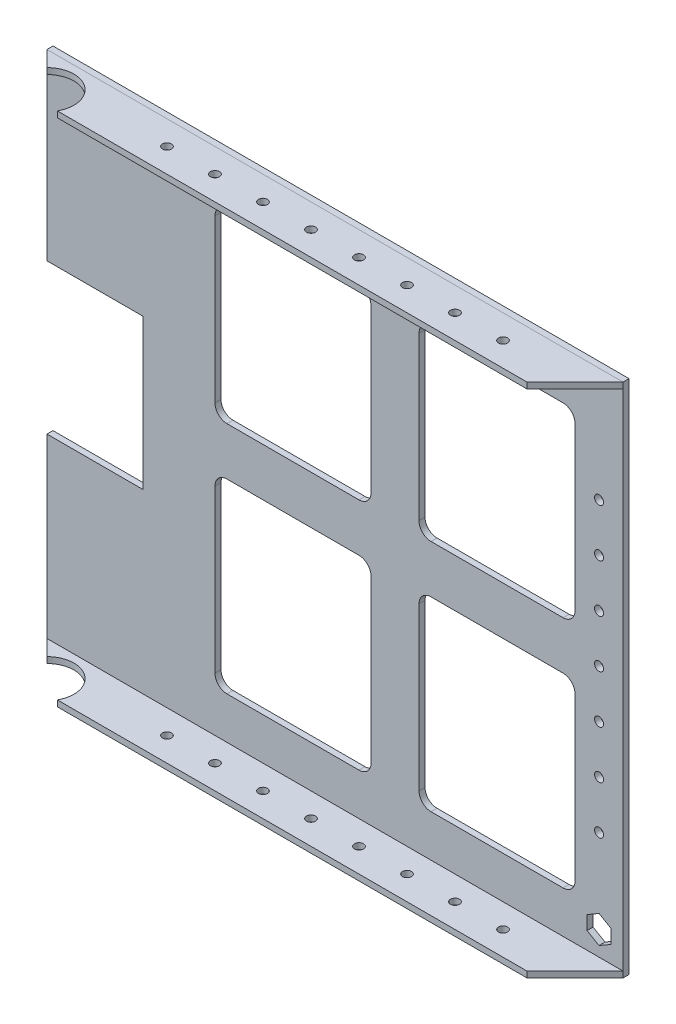
SolidWorks part; units mm, degrees
ref_plane "Front Plane" through (0, 0, 0) normal (0, 0, 1) x (1, 0, 0)
ref_plane "Top Plane" through (0, 0, 0) normal (0, 1, 0) x (1, 0, 0)
ref_plane "Right Plane" through (0, 0, 0) normal (1, 0, 0) x (0, 0, -1)
sketch "Sketch1" plane through (0, 0, 0) normal (0, 0, 1) x (1, 0, 0)
  line L1 (0, 0) -> (304.8, 0)
  line L2 (0, 0) -> (0, 273.05)
  line L3 (0, 273.05) -> (304.8, 273.05)
  line L4 (304.8, 0) -> (304.8, 273.05)
  dimension "D1" = 273.05
  dimension "D2" = 304.8
extrude "Boss-Extrude1" add sketch "Sketch1" along normal blind 3.175
sketch "Sketch2" plane through (0, 0, 3.175) normal (0, 0, 1) x (1, 0, 0)
  line L0 (0, 273.05) -> (0, 0) construction
  line L1 (95.25, 247.65) -> (165.1, 247.65)
  line L2 (88.9, 241.3) -> (88.9, 155.575)
  line L3 (95.25, 149.225) -> (165.1, 149.225)
  line L4 (279.4, 241.3) -> (279.4, 155.575)
  line L5 (95.25, 123.825) -> (165.1, 123.825)
  line L6 (88.9, 117.475) -> (88.9, 31.75)
  line L7 (95.25, 25.4) -> (165.1, 25.4)
  line L8 (279.4, 117.475) -> (279.4, 31.75)
  line L9 (0, 176.2125) -> (50.8, 176.2125)
  line L10 (0, 176.2125) -> (0, 96.8375)
  line L11 (0, 96.8375) -> (50.8, 96.8375)
  line L12 (50.8, 176.2125) -> (50.8, 96.8375)
  line L13 (304.8, 0) -> (304.8, 273.05) construction
  line L14 (304.8, 273.05) -> (0, 273.05) construction
  line L15 (0, 0) -> (304.8, 0) construction
  line L16 (-17.1716, 136.525) -> (403.4647, 136.525) construction
  line L17 (171.45, 241.3) -> (171.45, 155.575)
  line L18 (196.85, 241.3) -> (196.85, 155.575)
  line L19 (171.45, 117.475) -> (171.45, 31.75)
  line L20 (196.85, 117.475) -> (196.85, 31.75)
  line L21 (203.2, 247.65) -> (273.05, 247.65)
  line L22 (203.2, 149.225) -> (273.05, 149.225)
  line L23 (203.2, 123.825) -> (273.05, 123.825)
  line L24 (203.2, 25.4) -> (273.05, 25.4)
  arc A0 (95.25, 123.825) -> (88.9, 117.475) centre (95.25, 117.475) ccw
  arc A1 (88.9, 31.75) -> (95.25, 25.4) centre (95.25, 31.75) ccw
  arc A2 (273.05, 25.4) -> (279.4, 31.75) centre (273.05, 31.75) ccw
  arc A3 (273.05, 123.825) -> (279.4, 117.475) centre (273.05, 117.475) cw
  arc A4 (88.9, 155.575) -> (95.25, 149.225) centre (95.25, 155.575) ccw
  arc A5 (273.05, 149.225) -> (279.4, 155.575) centre (273.05, 155.575) ccw
  arc A6 (273.05, 247.65) -> (279.4, 241.3) centre (273.05, 241.3) cw
  arc A7 (95.25, 247.65) -> (88.9, 241.3) centre (95.25, 241.3) ccw
  arc A8 (196.85, 31.75) -> (203.2, 25.4) centre (203.2, 31.75) ccw
  arc A9 (171.45, 31.75) -> (165.1, 25.4) centre (165.1, 31.75) cw
  arc A10 (196.85, 117.475) -> (203.2, 123.825) centre (203.2, 117.475) cw
  arc A11 (171.45, 117.475) -> (165.1, 123.825) centre (165.1, 117.475) ccw
  arc A12 (196.85, 155.575) -> (203.2, 149.225) centre (203.2, 155.575) ccw
  arc A13 (171.45, 155.575) -> (165.1, 149.225) centre (165.1, 155.575) cw
  arc A14 (196.85, 241.3) -> (203.2, 247.65) centre (203.2, 241.3) cw
  arc A15 (171.45, 241.3) -> (165.1, 247.65) centre (165.1, 241.3) ccw
  point P48 (196.85, 25.4)
  point P53 (196.85, 123.825)
  point P58 (196.85, 149.225)
  point P61 (171.45, 149.225)
  point P64 (196.85, 247.65)
  dimension "D11" = 6.35
  dimension "D15" = 6.35
  dimension "D1" = 25.4
  dimension "D2" = 25.4
  dimension "D3" = 25.4
  dimension "D4" = 25.4
  dimension "D5" = 25.4
  dimension "D6" = 38.1
  dimension "D7" = 38.1
  dimension "D8" = 50.8
  dimension "D9" = 79.375
  dimension "D10" = 136.525
  dimension "D12" = 39.6875
  dimension "D13" = 25.4
  dimension "D14" = 25.4
extrude "Cut-Extrude1" cut sketch "Sketch2" against normal blind 3.175 normal cut yes
sketch "Sketch4" plane through (0, 0, 3.175) normal (0, 0, 1) x (1, 0, 0)
  line L0 (304.8, 0) -> (304.8, 273.05) construction
  line L1 (0, 273.05) -> (304.8, 273.05)
  line L2 (0, 273.05) -> (0, 269.875)
  line L3 (0, 269.875) -> (304.8, 269.875)
  line L4 (304.8, 273.05) -> (304.8, 269.875)
  dimension "D1" = 3.175
sketch "Sketch5" plane through (0, 0, 3.175) normal (0, 0, 1) x (1, 0, 0)
  line L1 (0, 273.05) -> (304.8, 273.05)
  line L2 (0, 273.05) -> (0, 269.875)
  line L3 (0, 269.875) -> (304.8, 269.875)
  line L4 (304.8, 273.05) -> (304.8, 269.875)
base flange "Base-Flange1" sketch "Sketch5" thickness 25.4 reverse thickness direction yes parameters "D1"=0.7366
chamfer "Chamfer1" distance 25.4 angle 45 2 edges at (0, 271.4625, 28.575) (304.8, 271.4625, 28.575)
sketch "Sketch10" plane through (0, 0, 3.175) normal (0, 0, 1) x (1, 0, 0)
  line L0 (304.8, 0) -> (304.8, 273.05) construction
  line L1 (0, 0) -> (304.8, 0)
  line L2 (0, 0) -> (0, 3.175)
  line L3 (0, 3.175) -> (304.8, 3.175)
  line L4 (304.8, 0) -> (304.8, 3.175)
  dimension "D1" = 3.175
base flange "Base-Flange2" sketch "Sketch10" thickness 25.4 reverse thickness direction yes parameters "D1"=0.7366
chamfer "Chamfer2" distance 25.4 angle 45 2 edges at (0, 1.5875, 28.575) (304.8, 1.5875, 28.575)
sketch "Sketch13" plane through (0, 273.05, 0) normal (0, 1, 0) x (1, 0, 0)
  line L1 (304.8, 0) -> (0, 0) construction
  line L3 (0, -3.175) -> (0, 0) construction
  circle A0 centre (18.415, -21.59) radius 14.2875
  dimension "D3" = 18.415
  dimension "D1" = 28.575
  dimension "D2" = 21.59
extrude "Cut-Extrude4" cut sketch "Sketch13" against normal through all normal cut yes
sketch "Sketch14" plane through (0, 0, 0) normal (0, 0, -1) x (-1, 0, 0)
  line L0 (-304.8, 273.05) -> (0, 273.05) construction
  line L1 (-38.1, 273.05) -> (-12.7, 273.05)
  line L2 (-38.1, 273.05) -> (-38.1, 269.875)
  line L3 (-38.1, 269.875) -> (-12.7, 269.875)
  line L4 (-12.7, 273.05) -> (-12.7, 269.875)
  line L5 (0, 273.05) -> (0, 176.2125) construction
  dimension "D1" = 3.175
  dimension "D2" = 25.4
  dimension "D3" = 12.7
sketch "Sketch19" plane through (0, 273.05, 0) normal (0, 1, 0) x (1, 0, 0)
  line L0 (-49.272, -15.875) -> (322.0215, -15.875) construction
  line L1 (279.4, -28.575) -> (30.8786, -28.575) construction
  circle A0 centre (76.2, -15.875) radius 2.3813
  circle A1 centre (101.6, -15.875) radius 2.3813
  circle A2 centre (127, -15.875) radius 2.3813
  circle A3 centre (152.4, -15.875) radius 2.3813
  circle A4 centre (177.8, -15.875) radius 2.3813
  circle A5 centre (203.2, -15.875) radius 2.3813
  circle A6 centre (228.6, -15.875) radius 2.3813
  circle A7 centre (254, -15.875) radius 2.3813
  dimension "D8" = 4.7625
  dimension "D1" = 12.7
  dimension "D2" = 25.4
  dimension "D3" = 25.4
  dimension "D4" = 25.4
  dimension "D5" = 25.4
  dimension "D6" = 25.4
  dimension "D7" = 76.2
  dimension "D9" = 25.4
  dimension "D10" = 25.4
extrude "Cut-Extrude7" cut sketch "Sketch19" against normal through all normal cut yes
sketch "Sketch20" plane through (0, 0, 0) normal (0, 0, -1) x (-1, 0, 0)
  line L0 (-292.1, 281.8115) -> (-292.1, -48.566) construction
  line L1 (-304.8, 0) -> (-304.8, 273.05) construction
  line L2 (-356.7906, 136.525) -> (75.1704, 136.525) construction
  line L3 (0, 273.05) -> (-304.8, 273.05) construction
  circle A0 centre (-292.1, 136.525) radius 2.3813
  circle A1 centre (-292.1, 161.925) radius 2.3813
  circle A2 centre (-292.1, 187.325) radius 2.3813
  circle A3 centre (-292.1, 212.725) radius 2.3813
  circle A4 centre (-292.1, 111.125) radius 2.3813
  circle A5 centre (-292.1, 85.725) radius 2.3813
  circle A6 centre (-292.1, 60.325) radius 2.3813
  dimension "D3" = 4.7625
  dimension "D1" = 12.7
  dimension "D2" = 136.525
  dimension "D4" = 25.4
  dimension "D5" = 50.8
  dimension "D6" = 25.4
  dimension "D7" = 25.4
  dimension "D8" = 25.4
  dimension "D9" = 50.8
extrude "Cut-Extrude8" cut sketch "Sketch20" against normal blind 50.8 normal cut yes
sketch "Sketch21" plane through (0, 3.175, 0) normal (0, 1, 0) x (1, 0, 0)
  circle A0 centre (18.415, -21.59) radius 14.2875
  arc A1 (30.8786, -28.575) -> (8.3122, -11.4872) centre (18.415, -21.59) ccw construction
  dimension "D1" = 28.575
extrude "Cut-Extrude9" cut sketch "Sketch21" against normal blind 3.175 normal cut yes
sketch "Sketch23" plane through (0, 0, 0) normal (0, 0, -1) x (-1, 0, 0)
  line L0 (0, 0) -> (-304.8, 0) construction
  line L1 (-292.1, 23.2073) -> (-298.45, 19.5412)
  line L2 (-298.45, 19.5412) -> (-298.45, 12.2088)
  line L3 (-298.45, 12.2088) -> (-292.1, 8.5427)
  line L4 (-292.1, 8.5427) -> (-285.75, 12.2088)
  line L5 (-285.75, 12.2088) -> (-285.75, 19.5412)
  line L6 (-285.75, 19.5412) -> (-292.1, 23.2073)
  line L7 (-304.8, 0) -> (-304.8, 273.05) construction
  line L8 (-292.1, 15.875) -> (-292.1, 23.2073) construction
  circle A0 centre (-292.1, 15.875) radius 6.35 construction
  dimension "D1" = 12.7
  dimension "D2" = 15.875
  dimension "D3" = 12.7
extrude "Cut-Extrude10" cut sketch "Sketch23" against normal through all contours L6 L1 L2 L3 L4 L5 normal cut yes
sketch "Bend-Lines1" [suppressed] plane through (0, 0, 0) normal (0, 1, 0) x (1, 0, 0)
sketch "Bounding-Box1" [suppressed] plane through (0, 0, 0) normal (0, 1, 0) x (1, 0, 0)
sheet metal parameters "Sheet-Metal3" thickness 25.4 parameters "D1"=0.7366
flat pattern "Flat-Pattern3" [suppressed]
sketch "Bend-Lines2" plane through (0, 0, 0) normal (0, 1, 0) x (1, 0, 0)
sketch3d "Bounding-Box2" [suppressed]
  line L0 (0, 269.875, 0) -> (-304.8, 269.875, 0) construction
  line L1 (0, 273.05, 0) -> (-304.8, 273.05, 0) construction
  line L2 (0, 269.875, 0) -> (0, 273.05, 0) construction
  line L3 (-304.8, 269.875, 0) -> (-304.8, 273.05, 0) construction
sheet metal parameters "Sheet-Metal4" thickness 25.4 parameters "D1"=0.7366
flat pattern "Flat-Pattern4"
sketch "Bend-Lines3" plane through (0, 0, 0) normal (0, 1, 0) x (1, 0, 0)
sketch3d "Bounding-Box3" [suppressed]
  line L0 (0, 0, 0) -> (-304.8, 0, 0) construction
  line L1 (0, 3.175, 0) -> (-304.8, 3.175, 0) construction
  line L2 (0, 0, 0) -> (0, 3.175, 0) construction
  line L3 (-304.8, 0, 0) -> (-304.8, 3.175, 0) construction
sheet metal parameters "Sheet-Metal5" thickness 25.4 parameters "D1"=0.7366
flat pattern "Flat-Pattern3"
sketch "Bend-Lines2" plane through (0, 0, 0) normal (0, 1, 0) x (1, 0, 0)
sketch3d "Bounding-Box2" [suppressed]
  line L0 (0, 269.875, 0) -> (-304.8, 269.875, 0) construction
  line L1 (0, 273.05, 0) -> (-304.8, 273.05, 0) construction
  line L2 (0, 269.875, 0) -> (0, 273.05, 0) construction
  line L3 (-304.8, 269.875, 0) -> (-304.8, 273.05, 0) construction
sheet metal parameters "Sheet-Metal9" thickness 25.4 parameters "D1"=0.7366
flat pattern "Flat-Pattern4"
sketch "Bend-Lines3" plane through (0, 0, 0) normal (0, 1, 0) x (1, 0, 0)
sketch3d "Bounding-Box3" [suppressed]
  line L0 (0, 0, 0) -> (-304.8, 0, 0) construction
  line L1 (0, 3.175, 0) -> (-304.8, 3.175, 0) construction
  line L2 (0, 0, 0) -> (0, 3.175, 0) construction
  line L3 (-304.8, 0, 0) -> (-304.8, 3.175, 0) construction
sheet metal parameters "Sheet-Metal10" thickness 25.4 parameters "D1"=0.7366
flat pattern "Flat-Pattern3"
sketch "Bend-Lines2" plane through (0, 0, 0) normal (0, 1, 0) x (1, 0, 0)
sketch3d "Bounding-Box2" [suppressed]
  line L0 (0, 269.875, 0) -> (-304.8, 269.875, 0) construction
  line L1 (0, 273.05, 0) -> (-304.8, 273.05, 0) construction
  line L2 (0, 269.875, 0) -> (0, 273.05, 0) construction
  line L3 (-304.8, 269.875, 0) -> (-304.8, 273.05, 0) construction
sheet metal parameters "Sheet-Metal12" thickness 25.4 parameters "D1"=0.7366
flat pattern "Flat-Pattern12"
sketch "Bend-Lines5" plane through (0, 0, 0) normal (0, 1, 0) x (1, 0, 0)
sketch3d "Bounding-Box5" [suppressed]
  line L0 (0, 269.875, 0) -> (-5.5014, 269.875, 0) construction
  line L1 (0, 273.05, 0) -> (-5.5014, 273.05, 0) construction
  line L2 (0, 269.875, 0) -> (0, 273.05, 0) construction
  line L3 (-5.5014, 269.875, 0) -> (-5.5014, 273.05, 0) construction
sheet metal parameters "Sheet-Metal13" thickness 25.4 parameters "D1"=0.7366
flat pattern "Flat-Pattern13"
sketch "Bend-Lines6" plane through (0, 0, 0) normal (0, 1, 0) x (1, 0, 0)
sketch3d "Bounding-Box6" [suppressed]
  line L0 (-31.3286, 269.875, 0) -> (-304.8, 269.875, 0) construction
  line L1 (-31.3286, 273.05, 0) -> (-304.8, 273.05, 0) construction
  line L2 (-31.3286, 269.875, 0) -> (-31.3286, 273.05, 0) construction
  line L3 (-304.8, 269.875, 0) -> (-304.8, 273.05, 0) construction
sheet metal parameters "Sheet-Metal15" thickness 25.4 parameters "D1"=0.7366
flat pattern "Flat-Pattern4"
sketch "Bend-Lines3" plane through (0, 0, 0) normal (0, 1, 0) x (1, 0, 0)
sketch3d "Bounding-Box3" [suppressed]
  line L0 (0, 0, 0) -> (-304.8, 0, 0) construction
  line L1 (0, 3.175, 0) -> (-304.8, 3.175, 0) construction
  line L2 (0, 0, 0) -> (0, 3.175, 0) construction
  line L3 (-304.8, 0, 0) -> (-304.8, 3.175, 0) construction
